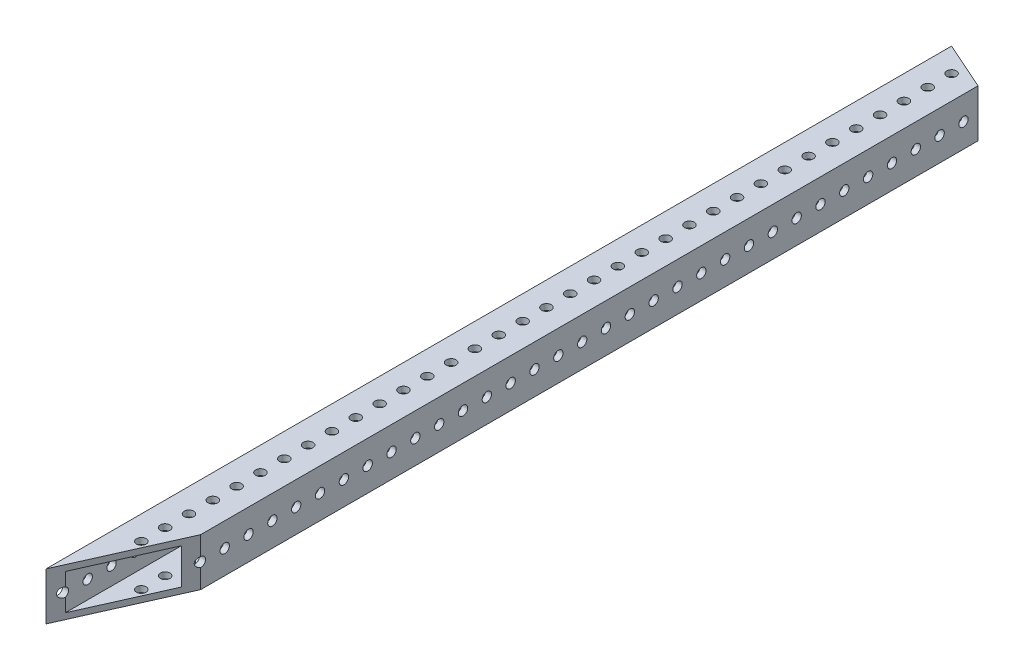
SolidWorks part; units mm, degrees
material "6061-T6 (SS)"
ref_plane "Front Plane" through (0, 0, 0) normal (0, 0, 1) x (1, 0, 0)
ref_plane "Top Plane" through (0, 0, 0) normal (0, 1, 0) x (1, 0, 0)
ref_plane "Right Plane" through (0, 0, 0) normal (1, 0, 0) x (0, 0, -1)
sketch "Sketch1" plane through (0, 0, 0) normal (0, 0, 1) x (1, 0, 0)
  line L0 (-9.525, 9.525) -> (9.525, 9.525)
  line L1 (-12.7, 12.7) -> (12.7, 12.7)
  line L2 (-12.7, 12.7) -> (-12.7, -12.7)
  line L3 (-12.7, -12.7) -> (12.7, -12.7)
  line L4 (12.7, 12.7) -> (12.7, -12.7)
  line L5 (9.525, 9.525) -> (9.525, -9.525)
  line L6 (-9.525, -9.525) -> (9.525, -9.525)
  line L7 (-9.525, 9.525) -> (-9.525, -9.525)
  line L8 (-12.7, 12.7) -> (12.7, -12.7) construction
  line L9 (12.7, 12.7) -> (-12.7, -12.7) construction
  point P5 (0, 0)
  dimension "D1" = 25.4
  dimension "D2" = 25.4
  dimension "D3" = 3.175
extrude "Boss-Extrude1" add sketch "Sketch1" along normal mid plane 482.6
sketch "Sketch2" plane through (0, 12.7, 0) normal (0, 1, 0) x (1, 0, 0)
  circle A2 centre (0, -292.1) radius 2.5527 construction
  circle A3 centre (0, -279.4) radius 2.5527 construction
  circle A6 centre (0, -266.7) radius 2.5527
  circle A9 centre (0, -254) radius 2.5527
  circle A12 centre (0, -241.3) radius 2.5527
  circle A15 centre (0, -228.6) radius 2.5527 construction
  circle A18 centre (0, -215.9) radius 2.5527 construction
  circle A21 centre (0, -203.2) radius 2.5527
  circle A24 centre (0, -190.5) radius 2.5527
  circle A27 centre (0, -177.8) radius 2.5527
  circle A30 centre (0, -165.1) radius 2.5527
  circle A33 centre (0, -152.4) radius 2.5527
  circle A36 centre (0, -139.7) radius 2.5527
  circle A39 centre (0, -127) radius 2.5527
  circle A42 centre (0, -114.3) radius 2.5527
  circle A45 centre (0, -101.6) radius 2.5527
  circle A48 centre (0, -88.9) radius 2.5527
  circle A51 centre (0, -76.2) radius 2.5527
  circle A54 centre (0, -63.5) radius 2.5527
  circle A57 centre (0, -50.8) radius 2.5527
  circle A60 centre (0, -38.1) radius 2.5527
  circle A63 centre (0, -25.4) radius 2.5527
  circle A66 centre (0, -12.7) radius 2.5527
  circle A69 centre (0, 0) radius 2.5527
  circle A72 centre (0, 12.7) radius 2.5527
  circle A75 centre (0, 25.4) radius 2.5527
  circle A78 centre (0, 38.1) radius 2.5527
  circle A81 centre (0, 50.8) radius 2.5527
  circle A84 centre (0, 63.5) radius 2.5527
  circle A87 centre (0, 76.2) radius 2.5527
  circle A90 centre (0, 88.9) radius 2.5527
  circle A93 centre (0, 101.6) radius 2.5527
  circle A96 centre (0, 114.3) radius 2.5527
  circle A99 centre (0, 127) radius 2.5527
  circle A108 centre (0, 152.4) radius 2.5527 [skipped]
  circle A111 centre (0, 139.7) radius 2.5527 [skipped]
  circle A116 centre (0, 139.7) radius 2.5527
  circle A119 centre (0, 152.4) radius 2.5527
  circle A122 centre (0, 165.1) radius 2.5527
  circle A125 centre (0, 177.8) radius 2.5527
  circle A128 centre (0, 190.5) radius 2.5527
  circle A131 centre (0, 203.2) radius 2.5527
  circle A134 centre (0, 215.9) radius 2.5527
  circle A137 centre (0, 228.6) radius 2.5527
  circle A140 centre (0, 241.3) radius 2.5527
  circle A143 centre (0, 254) radius 2.5527
  circle A146 centre (0, 266.7) radius 2.5527
  circle A149 centre (0, 279.4) radius 2.5527
  circle A152 centre (0, 292.1) radius 2.5527
  dimension "D6" = 12.7
  dimension "D5" = 36
  dimension "D8" = 14
extrude "Cut-Extrude1" cut sketch "Sketch2" against normal through all
sketch "Sketch4" plane through (12.7, 0, 0) normal (1, 0, 0) x (0, 0, -1)
  line L1 (-241.3, -12.7) -> (-241.3, 12.7) construction
  line L2 (-241.3, -12.7) -> (241.3, -12.7) construction
  circle A2 centre (-234.95, 0) radius 2.4892
  circle A3 centre (-222.25, 0) radius 2.4892
  circle A16 centre (-209.55, 0) radius 2.4892
  circle A17 centre (-196.85, 0) radius 2.4892
  circle A18 centre (-184.15, 0) radius 2.4892
  circle A19 centre (196.85, 0) radius 2.4892
  circle A20 centre (209.55, 0) radius 2.4892
  circle A21 centre (222.25, 0) radius 2.4892
  circle A22 centre (234.95, 0) radius 2.4892
  circle A23 centre (247.65, 0) radius 2.4892
  circle A24 centre (260.35, 0) radius 2.4892
  circle A25 centre (273.05, 0) radius 2.4892
  circle A26 centre (285.75, 0) radius 2.4892
  circle A27 centre (298.45, 0) radius 2.4892
  circle A28 centre (311.15, 0) radius 2.4892
  circle A29 centre (323.85, 0) radius 2.4892
  circle A30 centre (336.55, 0) radius 2.4892
  circle A31 centre (349.25, 0) radius 2.4892
  circle A32 centre (361.95, 0) radius 2.4892
  circle A35 centre (-171.45, 0) radius 2.4892
  circle A36 centre (-158.75, 0) radius 2.4892
  circle A37 centre (-146.05, 0) radius 2.4892
  circle A38 centre (-133.35, 0) radius 2.4892
  circle A39 centre (-120.65, 0) radius 2.4892
  circle A40 centre (-107.95, 0) radius 2.4892
  circle A41 centre (-95.25, 0) radius 2.4892
  circle A42 centre (-82.55, 0) radius 2.4892
  circle A43 centre (-69.85, 0) radius 2.4892
  circle A44 centre (-57.15, 0) radius 2.4892
  circle A45 centre (-44.45, 0) radius 2.4892
  circle A46 centre (-31.75, 0) radius 2.4892
  circle A47 centre (-19.05, 0) radius 2.4892
  circle A48 centre (-6.35, 0) radius 2.4892
  circle A49 centre (6.35, 0) radius 2.4892
  circle A50 centre (19.05, 0) radius 2.4892
  circle A51 centre (31.75, 0) radius 2.4892
  circle A52 centre (44.45, 0) radius 2.4892
  circle A53 centre (57.15, 0) radius 2.4892
  circle A54 centre (69.85, 0) radius 2.4892
  circle A55 centre (82.55, 0) radius 2.4892
  circle A56 centre (95.25, 0) radius 2.4892
  circle A57 centre (107.95, 0) radius 2.4892
  circle A58 centre (120.65, 0) radius 2.4892
  circle A59 centre (133.35, 0) radius 2.4892
  circle A60 centre (146.05, 0) radius 2.4892
  circle A61 centre (158.75, 0) radius 2.4892
  circle A62 centre (171.45, 0) radius 2.4892
  circle A63 centre (184.15, 0) radius 2.4892
  dimension "D2" = 4.9784
  dimension "D1" = 6.35
  dimension "D3" = 12.7
  dimension "D4" = 12.7
  dimension "D5" = 34
  dimension "D6" = 10
  dimension "D7" = 6
extrude "Cut-Extrude3" cut sketch "Sketch4" against normal through all
sketch "Sketch6" plane through (0, 12.7, 0) normal (0, 1, 0) x (1, 0, 0)
  line L4 (-12.7, -241.3) -> (12.7, -184.2507)
  line L5 (12.7, -241.3) -> (12.7, 241.3) construction
  line L6 (12.7, -184.2507) -> (12.7, -241.3)
  line L7 (12.7, -241.3) -> (-12.7, -241.3)
  dimension "D2" = 66
sketch "Sketch7" plane through (0, 12.7, 0) normal (0, 1, 0) x (1, 0, 0)
  line L0 (-12.7, 241.3) -> (12.7, 229.9912)
  line L1 (12.7, -241.3) -> (12.7, 241.3) construction
  line L2 (12.7, 229.9912) -> (12.7, 241.3)
  line L3 (12.7, 241.3) -> (-12.7, 241.3)
  dimension "D1" = 24
extrude "Cut-Extrude4" cut sketch "Sketch6" against normal through all
extrude "Cut-Extrude5" cut sketch "Sketch7" against normal through all
